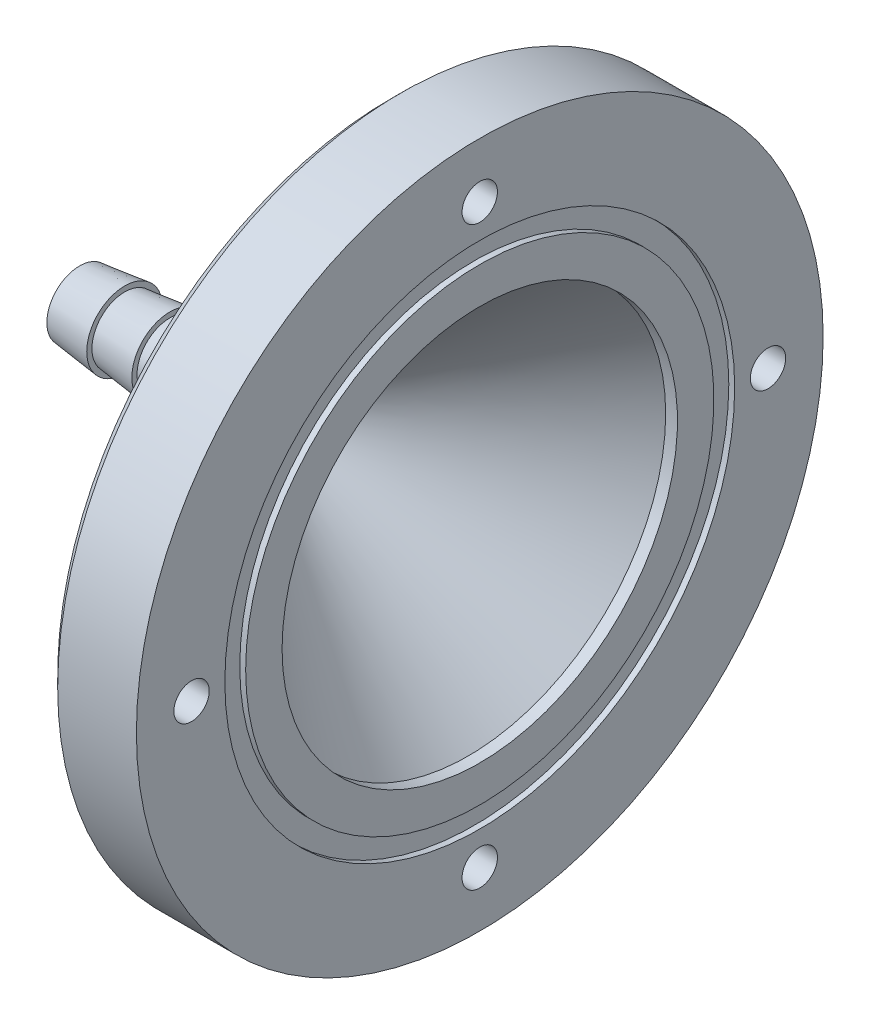
SolidWorks part; units mm, degrees
ref_plane "Front Plane" through (0, 0, 0) normal (0, 0, 1) x (1, 0, 0)
ref_plane "Top Plane" through (0, 0, 0) normal (0, 1, 0) x (1, 0, 0)
ref_plane "Right Plane" through (0, 0, 0) normal (1, 0, 0) x (0, 0, -1)
sketch "Sketch1" plane through (0, 0, 0) normal (0, 0, 1) x (1, 0, 0)
  line L0 (-801.9206, 0) -> (36107.5283, 0) construction
  line L3 (-14.1752, 3.65) -> (-14.1752, 3.15)
  line L8 (-18.5085, 1.9) -> (0, 1.9)
  line L9 (-18.5085, 1.9) -> (-18.5085, 3.15)
  line L10 (19.9465, 24.5) -> (19.9465, 33)
  line L12 (19.9465, 33) -> (11.3805, 33)
  line L16 (19.9465, 24.5) -> (19.3805, 24.5)
  line L17 (19.3805, 24.5) -> (19.3805, 19)
  line L18 (11.3805, 33) -> (11.3805, 19)
  line L20 (0, 1.9) -> (18.8145, 19)
  line L21 (-18.5085, 3.15) -> (-14.1752, 3.65)
  line L22 (18.8145, 19) -> (19.3805, 19)
  line L23 (-14.1752, 3.15) -> (-9.8419, 3.65)
  line L25 (-9.8419, 3.15) -> (-5.5085, 3.65)
  line L26 (-9.8419, 3.65) -> (-9.8419, 3.15)
  line L27 (-5.5085, 3.65) -> (11.3805, 19)
  line L33 (19.3805, 22.5) -> (19.9465, 22.5)
  line L34 (19.9465, 22.5) -> (19.9465, 19)
  line L35 (19.9465, 19) -> (19.3805, 19)
  dimension "D3" = 0.566
  dimension "D2" = 7.3
  dimension "D6" = 3.8
  dimension "D7" = 6.3
  dimension "D5" = 33
  dimension "D8" = 24.5
  dimension "D4" = 5
  dimension "D9" = 0.566
  dimension "D11" = 13
  dimension "D12" = 8.566
  dimension "D16" = 3.5
  dimension "D10" = 2
revolve "Revolve17" add sketch "Sketch1" angle 360 about L0 region at (-14.6698, 3.4, 0) region at (19.6635, 20.75, 0)
sketch "Sketch4" plane through (11.3805, 0, 0) normal (-1, 0, 0) x (0, 0, 1)
  line L0 (0, 19) -> (0, 33) construction
  circle A0 centre (0, 0) radius 27.7 construction
  circle A1 centre (0, 0) radius 19 construction
  circle A2 centre (0, 0) radius 33 construction
  point P3 (0, 27.7)
  point P7 (27.7, 0)
  point P12 (-27.7, 0)
  point P13 (0, -27.7)
  dimension "D1" = 5.3
  dimension "D2" = 5.3
hole_wizard "CBORE for M3 Hex Socket Head Cap Screw2" positions "Sketch4" profile "Sketch5" counterbore size "M3" standard "ISO"
sketch "Sketch5" plane through (11.3805, -27.7, 0) normal (0, 1, 0) x (0, 0, 1)
  line L0 (0, 0) -> (0, 9.5875)
  line L1 (0, 9.5875) -> (1.7, 8.566)
  line L2 (1.7, 8.566) -> (1.7, 3.4)
  line L3 (1.7, 3.4) -> (3.25, 3.4)
  line L4 (3.25, 3.4) -> (3.25, 0)
  line L5 (3.25, 0) -> (0, 0)
  line L10 (0, 9.5875) -> (-1.7, 8.566) construction
  line L11 (0, -6.35) -> (0, 107.95) construction
  dimension "Hole Dia." = 3.4
  dimension "Hole Depth" = 8.566
  dimension "C'Bore Dia." = 6.5
  dimension "C'Bore Depth" = 3.4
  dimension "Drill Angle" = 118
chamfer "Chamfer1" distance 1 angle 45 1 edges at (11.3805, 0, 33)
sketch "Sketch6" plane through (19.9465, 0, 0) normal (1, 0, 0) x (0, 0, -1)
  line L0 (0, 33) -> (0, 24.5)
  circle A0 centre (0, 0) radius 33
  circle A1 centre (0, 0) radius 33 construction
  circle A2 centre (0, 0) radius 24.5 construction
equation "\"D9@Sketch1\"=\"D3@Sketch1\""
